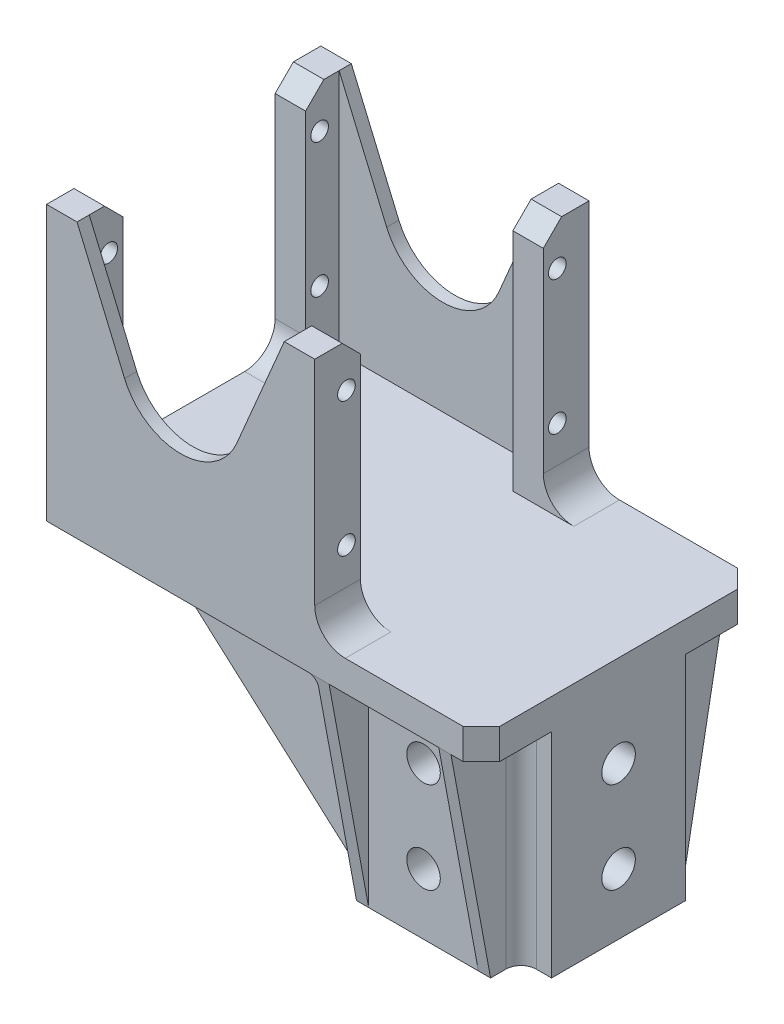
SolidWorks part; units mm, degrees
material "PLA"
ref_plane "Front Plane" through (0, 0, 0) normal (0, 0, 1) x (1, 0, 0)
ref_plane "Top Plane" through (0, 0, 0) normal (0, 1, 0) x (1, 0, 0)
ref_plane "Right Plane" through (0, 0, 0) normal (1, 0, 0) x (0, 0, -1)
sketch "Sketch2" plane through (0, 0, 0) normal (0, 0, 1) x (1, 0, 0)
  line L0 (12.8375, 22.5) -> (17.8375, 22.5) construction
  line L1 (-53.5125, 22.5) -> (17.8375, 22.5) construction
  line L2 (-17.8375, 22.5) -> (-17.8375, -22.5) construction
  line L3 (-53.5125, -22.5) -> (17.8375, -22.5)
  line L4 (17.8375, 22.5) -> (17.8375, -22.5) construction
  line L5 (-17.8375, 22.5) -> (17.8375, -22.5) construction
  line L6 (-17.8375, -22.5) -> (17.8375, 22.5) construction
  line L7 (-48.5125, 22.5) -> (12.8375, 22.5) construction
  line L8 (-17.8375, 22.5) -> (-17.8375, -17.5) construction
  line L9 (-48.5125, -17.5) -> (12.8375, -17.5) construction
  line L10 (12.8375, 22.5) -> (12.8375, -17.5) construction
  line L11 (-17.8375, 22.5) -> (12.8375, -17.5) construction
  line L12 (-17.8375, -17.5) -> (12.8375, 22.5) construction
  line L14 (-17.8375, -17.5) -> (-48.5125, 22.5) construction
  line L15 (-17.8375, 22.5) -> (-48.5125, -17.5) construction
  line L16 (-17.8375, -22.5) -> (-53.5125, 22.5) construction
  line L17 (-17.8375, 22.5) -> (-53.5125, -22.5) construction
  line L18 (-48.5125, 22.5) -> (-48.5125, -17.5)
  line L19 (-53.5125, 22.5) -> (-53.5125, -22.5)
  line L20 (-48.5125, 22.5) -> (-53.5125, 22.5)
  line L22 (-9.5125, -17.5) -> (-9.5125, 22.5)
  line L23 (-9.5125, 22.5) -> (-14.5125, 22.5)
  line L24 (-14.5125, 22.5) -> (-14.5125, -17.5)
  line L26 (17.8375, -17.5) -> (17.8375, -22.5)
  line L27 (-48.5125, -17.5) -> (-14.5125, -17.5)
  line L28 (-9.5125, -17.5) -> (17.8375, -17.5)
  point P4 (0, 0)
  point P8 (-2.5, 2.5)
  point P14 (-33.175, 2.5)
  point P15 (-35.675, 0)
  dimension "D1" = 5
  dimension "D2" = 40
  dimension "D3" = 27.35
  dimension "D4" = 5
  dimension "D5" = 34
  dimension "D6" = 5
extrude "Boss-Extrude1" add sketch "Sketch2" along normal blind 45
sketch "Sketch3" plane through (-53.5125, 0, 0) normal (1, 0, 0) x (0, 0, -1)
  line L0 (-5.2, 22.5) -> (-5.2, -22.5) construction
  line L2 (-39.8, 22.5) -> (-39.8, -22.5) construction
  line L4 (-37.5, 22.5) -> (-7.5, 22.5)
  line L5 (-37.5, 22.5) -> (-37.5, -17.5)
  line L6 (-37.5, -17.5) -> (-7.5, -17.5)
  line L7 (-7.5, 22.5) -> (-7.5, -17.5)
  line L8 (-37.5, 22.5) -> (-7.5, -17.5) construction
  line L9 (-37.5, -17.5) -> (-7.5, 22.5) construction
  line L10 (-45, 22.5) -> (0, 22.5) construction
  line L11 (-39.8, 15.5) -> (-5.2, 15.5) construction
  line L12 (-39.8, -6.5) -> (-5.2, -6.5) construction
  line L13 (-45, -22.5) -> (0, -22.5) construction
  circle A2 centre (-5.2, 15.5) radius 1.25 construction
  circle A3 centre (-5.2, -6.5) radius 1.25 construction
  circle A4 centre (-39.8, 15.5) radius 1.25 construction
  circle A5 centre (-39.8, -6.5) radius 1.25 construction
  point P10 (-22.5, 2.5)
  dimension "D4" = 2.3
  dimension "D7" = 2.5
  dimension "D5" = 2.5
  dimension "D6" = 2.5
  dimension "D9" = 2.5
  dimension "D8" = 22
  dimension "D1" = 30
  dimension "D2" = 5
  dimension "D3" = 2.3
  dimension "D10" = 11
extrude "Cut-Extrude1" cut sketch "Sketch3" along normal through all
sketch "Sketch4" plane through (0, -22.5, 0) normal (0, -1, 0) x (1, 0, 0)
  line L0 (-53.5125, 22.5) -> (17.8375, 22.5) construction
  line L1 (17.8375, 45) -> (17.8375, 0) construction
  line L3 (-53.5125, 45) -> (-53.5125, 0) construction
  line L10 (-8.4125, 32.75) -> (12.0875, 32.75)
  line L11 (-8.4125, 32.75) -> (-8.4125, 12.25)
  line L12 (-8.4125, 12.25) -> (12.0875, 12.25)
  line L13 (12.0875, 32.75) -> (12.0875, 12.25)
  line L14 (-8.4125, 32.75) -> (12.0875, 12.25) construction
  line L15 (-8.4125, 12.25) -> (12.0875, 32.75) construction
  line L16 (-14.1625, 38.5) -> (17.8375, 38.5)
  line L17 (-14.1625, 38.5) -> (-14.1625, 6.5)
  line L18 (-14.1625, 6.5) -> (17.8375, 6.5)
  line L19 (17.8375, 38.5) -> (17.8375, 6.5)
  line L20 (-14.1625, 38.5) -> (17.8375, 6.5) construction
  line L21 (-14.1625, 6.5) -> (17.8375, 38.5) construction
  circle A0 centre (1.8375, 22.5) radius 2.5
  point P18 (1.8375, 22.5)
  point P23 (1.8375, 22.5)
  dimension "D1" = 5
  dimension "D2" = 20.5
  dimension "D3" = 20.5
  dimension "D4" = 32
extrude "Boss-Extrude2" add sketch "Sketch4" along normal blind 35 contours L19 L16 L17 L18 L10 L13 L12 L11 region at (1.8375, -22.5, 38.0475)
sketch "Sketch5" plane through (0, 0, 38.5) normal (0, 0, 1) x (1, 0, 0)
  line L0 (1.8375, -22.5) -> (1.8375, -57.5) construction
  line L3 (-14.1625, -22.5) -> (17.8375, -22.5) construction
  line L4 (-14.1625, -57.5) -> (17.8375, -57.5) construction
  circle A0 centre (1.8375, -32.5) radius 2.5 construction
  circle A1 centre (1.8375, -47.5) radius 2.5 construction
  dimension "D2" = 5
  dimension "D3" = 5
  dimension "D4" = 10
  dimension "D1" = 15
sketch "Sketch6" plane through (0, -57.5, 0) normal (0, -1, 0) x (-1, 0, 0)
  line L1 (14.1625, -38.5) -> (9.1625, -38.5)
  line L2 (14.1625, -38.5) -> (14.1625, -33.5)
  line L3 (14.1625, -33.5) -> (9.1625, -33.5)
  line L4 (9.1625, -38.5) -> (9.1625, -33.5)
  line L5 (14.1625, -38.5) -> (9.1625, -33.5) construction
  line L6 (14.1625, -33.5) -> (9.1625, -38.5) construction
  line L7 (-17.8375, -38.5) -> (-12.8375, -38.5)
  line L8 (-17.8375, -38.5) -> (-17.8375, -33.5)
  line L9 (-17.8375, -33.5) -> (-12.8375, -33.5)
  line L10 (-12.8375, -38.5) -> (-12.8375, -33.5)
  line L11 (-17.8375, -38.5) -> (-12.8375, -33.5) construction
  line L12 (-17.8375, -33.5) -> (-12.8375, -38.5) construction
  line L13 (-17.8375, -6.5) -> (-12.8375, -6.5)
  line L14 (-17.8375, -6.5) -> (-17.8375, -11.5)
  line L15 (-17.8375, -11.5) -> (-12.8375, -11.5)
  line L16 (-12.8375, -6.5) -> (-12.8375, -11.5)
  line L17 (-17.8375, -6.5) -> (-12.8375, -11.5) construction
  line L18 (-17.8375, -11.5) -> (-12.8375, -6.5) construction
  line L19 (14.1625, -6.5) -> (9.1625, -6.5)
  line L20 (14.1625, -6.5) -> (14.1625, -11.5)
  line L21 (14.1625, -11.5) -> (9.1625, -11.5)
  line L22 (9.1625, -6.5) -> (9.1625, -11.5)
  line L23 (14.1625, -6.5) -> (9.1625, -11.5) construction
  line L24 (14.1625, -11.5) -> (9.1625, -6.5) construction
  point P4 (11.6625, -36)
  point P11 (-15.3375, -36)
  point P18 (-15.3375, -9)
  point P25 (11.6625, -9)
  dimension "D1" = 5
  dimension "D2" = 5
  dimension "D3" = 5
  dimension "D4" = 5
extrude "Cut-Extrude4" cut sketch "Sketch6" against normal up to surface (35 mm away) up to face at (-8, -22.5, 22.5)
sketch "Sketch9" plane through (0, 0, 33.5) normal (0, 0, 1) x (1, 0, 0)
  line L0 (-14.1625, -57.5) -> (-53.5125, -22.5)
  line L1 (-53.5125, -22.5) -> (17.8375, -22.5) construction
  line L2 (-53.5125, -22.5) -> (17.8375, -22.5) construction
rib "Rib1" sketch "Sketch9" sketch "Sketch9" thickness 2 extrusion direction parallel to sketch draft on no parameters "D1"=2
pattern_linear "LPattern1" count 2 spacing 20 along (0, 0, -1) of "Rib1"
sketch "Sketch14" plane through (12.8375, 0, 0) normal (1, 0, 0) x (0, 0, -1)
  line L0 (-6.5, -57.5) -> (0, -22.5)
rib "Rib6" sketch "Sketch14" sketch "Sketch14" thickness 2 extrusion direction parallel to sketch draft on no parameters "D1"=2
sketch "Sketch15" plane through (-9.1625, 0, 0) normal (-1, 0, 0) x (0, 0, 1)
  line L0 (6.5, -57.5) -> (0, -22.5)
rib "Rib7" sketch "Sketch15" sketch "Sketch15" thickness 2 extrusion direction parallel to sketch draft on no parameters "D1"=2
fillet "Fillet2" radius 5 3 edges at (-14.1625, -22.5, 22.5) (1.8375, -22.5, 6.5) (1.8375, -22.5, 38.5)
fillet "Fillet3" radius 5 2 edges at (-9.5125, -17.5, 3.75) (-9.5125, -17.5, 41.25)
sketch "Sketch17" plane through (0, 0, 45) normal (0, 0, 1) x (1, 0, 0)
  line L0 (-48.5125, 22.5) -> (-31.5125, -17.5)
  line L1 (-14.5125, -17.5) -> (-48.5125, -17.5) construction
rib "Rib10" sketch "Sketch17" sketch "Sketch17" thickness 2 extrusion direction parallel to sketch draft on no parameters "D1"=2
sketch "Sketch18" plane through (0, 0, 45) normal (0, 0, 1) x (1, 0, 0)
  line L0 (-31.5125, -17.5) -> (-14.5125, 22.5)
rib "Rib11" sketch "Sketch18" sketch "Sketch18" thickness 2 extrusion direction parallel to sketch draft on no parameters "D1"=2
fillet "Fillet4" radius 10 1 edges at (-31.5125, -17.5, 44)
pattern_linear "LPattern2" count 2 spacing 43 along (0, 0, -1) of "Fillet4", "Rib11", "Rib10"
hole_wizard "M5 Clearance Hole2" positions "Sketch20" profile "Sketch22" hole size "M5" standard "ISO"
sketch "Sketch20" plane through (0, 0, 38.5) normal (0, 0, 1) x (1, 0, 0)
  point P0 (1.8375, -32.5)
  point P3 (1.8375, -47.5)
sketch "Sketch22" plane through (1.8375, -32.5, 38.5) normal (1, 0, 0) x (0, -1, 0)
  line L0 (0, 0) -> (0, 7.6524)
  line L1 (0, 7.6524) -> (2.75, 6)
  line L2 (2.75, 6) -> (2.75, 0)
  line L5 (2.75, 0) -> (0, 0)
  line L10 (0, 7.6524) -> (-2.75, 6) construction
  line L11 (0, -6.35) -> (0, 107.95) construction
  dimension "Hole Dia." = 5.5
  dimension "Hole Depth" = 6
  dimension "Drill Angle" = 118
hole_wizard "M2.5 Clearance Hole1" positions "Sketch23" profile "Sketch24" hole size "M2.5" standard "ISO" end condition through all
sketch "Sketch23" plane through (-53.5125, 0, 0) normal (-1, 0, 0) x (0, 0, 1)
  point P0 (5.2, 15.5)
  point P3 (39.8, 15.5)
  point P6 (39.8, -6.5)
  point P9 (5.2, -6.5)
sketch "Sketch24" plane through (-53.5125, 15.5, 5.2) normal (0, 1, 0) x (0, 0, 1)
  line L0 (0, 0) -> (0, 71.35)
  line L1 (0, 71.35) -> (1.45, 71.35)
  line L2 (1.45, 71.35) -> (1.45, 0)
  line L5 (1.45, 0) -> (0, 0)
  line L11 (0, -6.35) -> (0, 107.95) construction
  dimension "Thru Hole Dia." = 2.9
  dimension "Thru Hole Depth" = 71.35
fillet "Fillet5" radius 2.5 4 edges at (-9.1625, -40, 11.5) (-9.1625, -40, 33.5) (12.8375, -40, 33.5) (12.8375, -40, 11.5)
extrude "Boss-Extrude4" add sketch "Sketch4<4>" along normal blind 8 contours A0 region at (1.8375, -22.5, 22.5)
sketch "Sketch4<4>" plane through (0, -22.5, 0) normal (0, -1, 0) x (1, 0, 0) same geometry as "Sketch4"
pattern_circular "CirPattern1" count 4 every 90 about axis through (1.8375, -30.5, 22.5) along (0, -1, 0) of "M5 Clearance Hole2"
ref_axis "Axis2" through (1.8375, -30.5, 22.5) along (0, 1, 0)
ref_plane "Plane1" through (0, 0, 22.5) normal (0, 0, 1) x (1, 0, 0)
mirror "Mirror1" about plane through (0, 0, 22.5) normal (0, 0, 1) of "Rib6", "Rib7"
chamfer "Chamfer1" distance 3 angle 45 6 edges at (17.8375, -20, 0) (17.8375, -20, 45) (-51.0125, 22.5, 37.5) (-51.0125, 22.5, 7.5) (-12.0125, 22.5, 7.5) (-12.0125, 22.5, 37.5)
fillet "Fillet6" radius 5 2 edges at (-51.0125, -17.5, 37.5) (-51.0125, -17.5, 7.5)
fillet "Fillet7" radius 1.5 12 edges at (-9.1625, -22.5, 4.5) (-9.8947, -22.5, 10.7678) (-14.1625, -42.5, 13.5) (-15.627, -23.9645, 13.5) (-14.1625, -42.5, 31.5) (-15.627, -23.9645, 31.5) (-9.1625, -22.5, 40.5) (-9.8947, -22.5, 34.2322) (-32.5875, -22.5, 11.5) (-36.3375, -22.5, 13.5) (-36.3375, -22.5, 31.5) (-32.5875, -22.5, 33.5)
